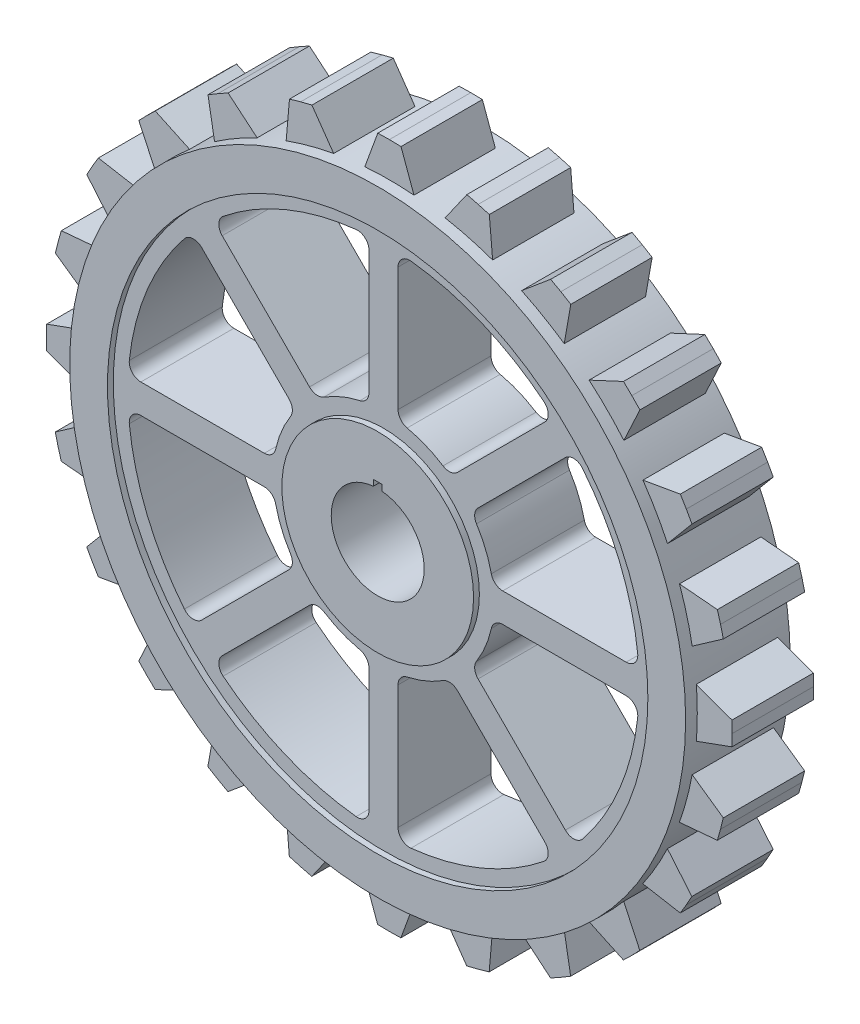
SolidWorks part; units mm, degrees
material "Cast Carbon Steel"
ref_plane "Front Plane" through (0, 0, 0) normal (0, 0, 1) x (1, 0, 0)
ref_plane "Top Plane" through (0, 0, 0) normal (0, 1, 0) x (1, 0, 0)
ref_plane "Right Plane" through (0, 0, 0) normal (1, 0, 0) x (0, 0, -1)
sketch "Sketch1" plane through (0, 0, 0) normal (0, 0, 1) x (1, 0, 0)
  circle A0 centre (-5.965, 13.7526) radius 59000 construction
  circle A1 centre (-5.965, 13.7526) radius 53000
  circle A2 centre (-5.965, 13.7526) radius 46500
extrude "Boss-Extrude4" add sketch "Sketch1" along normal blind 9000 and the other way blind 9000
sketch "Sketch2" plane through (0, 0, 0) normal (0, 0, 1) x (1, 0, 0)
  line L0 (-52494.638, 4371.0565) -> (-52496.6698, -4346.5861)
  line L1 (-58972.0667, 2013.4653) -> (-52494.638, 4371.0565)
  line L2 (-59005.965, 13.7526) -> (-58972.0667, 2013.4653)
  line L3 (-59005.965, 13.7526) -> (-58972.9988, -1985.9757)
  line L4 (-58972.9988, -1985.9757) -> (-52496.6698, -4346.5861)
  line L5 (-49574.6139, 17808.7285) -> (-51832.8684, 9388.6582)
  line L6 (-57477.551, 13345.03) -> (-51832.8684, 9388.6582)
  line L7 (-56991.826, 15285.1515) -> (-57477.551, 13345.03)
  line L8 (-56991.826, 15285.1515) -> (-56441.5191, 17207.9521)
  line L9 (-56441.5191, 17207.9521) -> (-49574.6139, 17808.7285)
  line L10 (-43276.1618, 30032.765) -> (-47636.7427, 22484.0809)
  line L11 (-52065.103, 27766.594) -> (-47636.7427, 22484.0809)
  line L12 (-51093.7884, 29514.8926) -> (-52065.103, 27766.594)
  line L13 (-51093.7884, 29514.8926) -> (-50064.5752, 31229.7454)
  line L14 (-50064.5752, 31229.7454) -> (-43276.1618, 30032.765)
  line L15 (-34028.5108, 40210.1182) -> (-40194.2517, 34047.2507)
  line L16 (-43104.5043, 40295.9105) -> (-40194.2517, 34047.2507)
  line L17 (-41713.7934, 41733.2425) -> (-43104.5043, 40295.9105)
  line L18 (-41713.7934, 41733.2425) -> (-40275.8133, 43123.2832)
  line L19 (-40275.8133, 43123.2832) -> (-34028.5108, 40210.1182)
  line L20 (-22461.873, 47647.2183) -> (-30012.5889, 43290.1566)
  line L21 (-31206.4048, 50079.1273) -> (-30012.5889, 43290.1566)
  line L22 (-29491.0724, 51107.5409) -> (-31206.4048, 50079.1273)
  line L23 (-29491.0724, 51107.5409) -> (-27742.3212, 52078.0405)
  line L24 (-27742.3212, 52078.0405) -> (-22461.873, 47647.2183)
  line L25 (-9364.4957, 51837.2393) -> (-17785.6177, 49582.9099)
  line L26 (-17181.6405, 56449.5343) -> (-17785.6177, 49582.9099)
  line L27 (-15258.5835, 56998.9449) -> (-17181.6405, 56449.5343)
  line L28 (-15258.5835, 56998.9449) -> (-13318.2359, 57483.7654)
  line L29 (-13318.2359, 57483.7654) -> (-9364.4957, 51837.2393)
  line L30 (4371.0565, 52494.638) -> (-4346.5861, 52496.6698)
  line L31 (-1985.9757, 58972.9988) -> (-4346.5861, 52496.6698)
  line L32 (13.7526, 59005.965) -> (-1985.9757, 58972.9988)
  line L33 (13.7526, 59005.965) -> (2013.4653, 58972.0667)
  line L34 (2013.4653, 58972.0667) -> (4371.0565, 52494.638)
  line L35 (17808.7285, 49574.6139) -> (9388.6582, 51832.8684)
  line L36 (13345.03, 57477.551) -> (9388.6582, 51832.8684)
  line L37 (15285.1515, 56991.826) -> (13345.03, 57477.551)
  line L38 (15285.1515, 56991.826) -> (17207.9521, 56441.5191)
  line L39 (17207.9521, 56441.5191) -> (17808.7285, 49574.6139)
  line L40 (30032.765, 43276.1618) -> (22484.0809, 47636.7427)
  line L41 (27766.594, 52065.103) -> (22484.0809, 47636.7427)
  line L42 (29514.8926, 51093.7884) -> (27766.594, 52065.103)
  line L43 (29514.8926, 51093.7884) -> (31229.7454, 50064.5752)
  line L44 (31229.7454, 50064.5752) -> (30032.765, 43276.1618)
  line L45 (40210.1182, 34028.5108) -> (34047.2507, 40194.2517)
  line L46 (40295.9105, 43104.5043) -> (34047.2507, 40194.2517)
  line L47 (41733.2425, 41713.7934) -> (40295.9105, 43104.5043)
  line L48 (41733.2425, 41713.7934) -> (43123.2832, 40275.8133)
  line L49 (43123.2832, 40275.8133) -> (40210.1182, 34028.5108)
  line L50 (47647.2183, 22461.873) -> (43290.1566, 30012.5889)
  line L51 (50079.1273, 31206.4048) -> (43290.1566, 30012.5889)
  line L52 (51107.5409, 29491.0724) -> (50079.1273, 31206.4048)
  line L53 (51107.5409, 29491.0724) -> (52078.0405, 27742.3212)
  line L54 (52078.0405, 27742.3212) -> (47647.2183, 22461.873)
  line L55 (51837.2393, 9364.4957) -> (49582.9099, 17785.6177)
  line L56 (56449.5343, 17181.6405) -> (49582.9099, 17785.6177)
  line L57 (56998.9449, 15258.5835) -> (56449.5343, 17181.6405)
  line L58 (56998.9449, 15258.5835) -> (57483.7654, 13318.2359)
  line L59 (57483.7654, 13318.2359) -> (51837.2393, 9364.4957)
  line L60 (52494.638, -4371.0565) -> (52496.6698, 4346.5861)
  line L61 (58972.9988, 1985.9757) -> (52496.6698, 4346.5861)
  line L62 (59005.965, -13.7526) -> (58972.9988, 1985.9757)
  line L63 (59005.965, -13.7526) -> (58972.0667, -2013.4653)
  line L64 (58972.0667, -2013.4653) -> (52494.638, -4371.0565)
  line L65 (49574.6139, -17808.7285) -> (51832.8684, -9388.6582)
  line L66 (57477.551, -13345.03) -> (51832.8684, -9388.6582)
  line L67 (56991.826, -15285.1515) -> (57477.551, -13345.03)
  line L68 (56991.826, -15285.1515) -> (56441.5191, -17207.9521)
  line L69 (56441.5191, -17207.9521) -> (49574.6139, -17808.7285)
  line L70 (43276.1618, -30032.765) -> (47636.7427, -22484.0809)
  line L71 (52065.103, -27766.594) -> (47636.7427, -22484.0809)
  line L72 (51093.7884, -29514.8926) -> (52065.103, -27766.594)
  line L73 (51093.7884, -29514.8926) -> (50064.5752, -31229.7454)
  line L74 (50064.5752, -31229.7454) -> (43276.1618, -30032.765)
  line L75 (34028.5108, -40210.1182) -> (40194.2517, -34047.2507)
  line L76 (43104.5043, -40295.9105) -> (40194.2517, -34047.2507)
  line L77 (41713.7934, -41733.2425) -> (43104.5043, -40295.9105)
  line L78 (41713.7934, -41733.2425) -> (40275.8133, -43123.2832)
  line L79 (40275.8133, -43123.2832) -> (34028.5108, -40210.1182)
  line L80 (22461.873, -47647.2183) -> (30012.5889, -43290.1566)
  line L81 (31206.4048, -50079.1273) -> (30012.5889, -43290.1566)
  line L82 (29491.0724, -51107.5409) -> (31206.4048, -50079.1273)
  line L83 (29491.0724, -51107.5409) -> (27742.3212, -52078.0405)
  line L84 (27742.3212, -52078.0405) -> (22461.873, -47647.2183)
  line L85 (9364.4957, -51837.2393) -> (17785.6177, -49582.9099)
  line L86 (17181.6405, -56449.5343) -> (17785.6177, -49582.9099)
  line L87 (15258.5835, -56998.9449) -> (17181.6405, -56449.5343)
  line L88 (15258.5835, -56998.9449) -> (13318.2359, -57483.7654)
  line L89 (13318.2359, -57483.7654) -> (9364.4957, -51837.2393)
  line L90 (-4371.0565, -52494.638) -> (4346.5861, -52496.6698)
  line L91 (1985.9757, -58972.9988) -> (4346.5861, -52496.6698)
  line L92 (-13.7526, -59005.965) -> (1985.9757, -58972.9988)
  line L93 (-13.7526, -59005.965) -> (-2013.4653, -58972.0667)
  line L94 (-2013.4653, -58972.0667) -> (-4371.0565, -52494.638)
  line L95 (-17808.7285, -49574.6139) -> (-9388.6582, -51832.8684)
  line L96 (-13345.03, -57477.551) -> (-9388.6582, -51832.8684)
  line L97 (-15285.1515, -56991.826) -> (-13345.03, -57477.551)
  line L98 (-15285.1515, -56991.826) -> (-17207.9521, -56441.5191)
  line L99 (-17207.9521, -56441.5191) -> (-17808.7285, -49574.6139)
  line L100 (-30032.765, -43276.1618) -> (-22484.0809, -47636.7427)
  line L101 (-27766.594, -52065.103) -> (-22484.0809, -47636.7427)
  line L102 (-29514.8926, -51093.7884) -> (-27766.594, -52065.103)
  line L103 (-29514.8926, -51093.7884) -> (-31229.7454, -50064.5752)
  line L104 (-31229.7454, -50064.5752) -> (-30032.765, -43276.1618)
  line L105 (-40210.1182, -34028.5108) -> (-34047.2507, -40194.2517)
  line L106 (-40295.9105, -43104.5043) -> (-34047.2507, -40194.2517)
  line L107 (-41733.2425, -41713.7934) -> (-40295.9105, -43104.5043)
  line L108 (-41733.2425, -41713.7934) -> (-43123.2832, -40275.8133)
  line L109 (-43123.2832, -40275.8133) -> (-40210.1182, -34028.5108)
  line L110 (-47647.2183, -22461.873) -> (-43290.1566, -30012.5889)
  line L111 (-50079.1273, -31206.4048) -> (-43290.1566, -30012.5889)
  line L112 (-51107.5409, -29491.0724) -> (-50079.1273, -31206.4048)
  line L113 (-51107.5409, -29491.0724) -> (-52078.0405, -27742.3212)
  line L114 (-52078.0405, -27742.3212) -> (-47647.2183, -22461.873)
  line L115 (-51837.2393, -9364.4957) -> (-49582.9099, -17785.6177)
  line L116 (-56449.5343, -17181.6405) -> (-49582.9099, -17785.6177)
  line L117 (-56998.9449, -15258.5835) -> (-56449.5343, -17181.6405)
  line L118 (-56998.9449, -15258.5835) -> (-57483.7654, -13318.2359)
  line L119 (-57483.7654, -13318.2359) -> (-51837.2393, -9364.4957)
  circle A0 centre (-5.965, 13.7526) radius 59000 construction
  point P125 (0, 0)
  dimension "D1" = 24
extrude "Boss-Extrude5" add sketch "Sketch2" along normal blind 7000 and the other way blind 7000
sketch "Sketch3" plane through (0, 0, 0) normal (0, 0, 1) x (1, 0, 0)
  line L2 (2500, 20512.1915) -> (2500, 41758.2327)
  line L3 (12736.5428, 16272.0767) -> (27759.7626, 31295.2965)
  line L4 (16272.0767, 12736.5428) -> (31295.2965, 27759.7626)
  line L5 (20512.1915, 2500) -> (41758.2327, 2500)
  line L6 (20512.1915, -2500) -> (41758.2327, -2500)
  line L7 (16272.0767, -12736.5428) -> (31295.2965, -27759.7626)
  line L8 (12736.5428, -16272.0767) -> (27759.7626, -31295.2965)
  line L9 (2500, -20512.1915) -> (2500, -41758.2327)
  line L10 (-2500, -20512.1915) -> (-2500, -41758.2327)
  line L11 (-12736.5428, -16272.0767) -> (-27759.7626, -31295.2965)
  line L12 (-16272.0767, -12736.5428) -> (-31295.2965, -27759.7626)
  line L13 (-20512.1915, -2500) -> (-41758.2327, -2500)
  line L14 (-20512.1915, 2500) -> (-41758.2327, 2500)
  line L15 (-16272.0767, 12736.5428) -> (-31295.2965, 27759.7626)
  line L16 (-12736.5428, 16272.0767) -> (-27759.7626, 31295.2965)
  line L17 (-2500, 20512.1915) -> (-2500, 41758.2327)
  arc A2 (27600.099, 34267.1058) -> (4714.2857, 43746.72) centre (0, 0) ccw
  arc A3 (10244.0121, 16001.8816) -> (4071.4286, 18558.6494) centre (0, 0) ccw
  arc A4 (31295.2965, 27759.7626) -> (34267.1058, 27600.099) centre (32709.51, 26345.549) cw
  arc A5 (2500, 20512.1915) -> (4071.4286, 18558.6494) centre (4500, 20512.1915) ccw
  arc A6 (12736.5428, 16272.0767) -> (10244.0121, 16001.8816) centre (11322.3292, 17686.2902) cw
  arc A7 (16272.0767, 12736.5428) -> (16001.8816, 10244.0121) centre (17686.2902, 11322.3292) ccw
  arc A8 (27600.099, 34267.1058) -> (27759.7626, 31295.2965) centre (26345.549, 32709.51) cw
  arc A9 (2500, 41758.2327) -> (4714.2857, 43746.72) centre (4500, 41758.2327) cw
  arc A10 (43746.72, 4714.2857) -> (34267.1058, 27600.099) centre (0, 0) ccw
  arc A11 (43746.72, 4714.2857) -> (41758.2327, 2500) centre (41758.2327, 4500) cw
  arc A12 (20512.1915, 2500) -> (18558.6494, 4071.4286) centre (20512.1915, 4500) cw
  arc A13 (18558.6494, 4071.4286) -> (16001.8816, 10244.0121) centre (0, 0) ccw
  arc A14 (41758.2327, -2500) -> (43746.72, -4714.2857) centre (41758.2327, -4500) cw
  arc A15 (20512.1915, -2500) -> (18558.6494, -4071.4286) centre (20512.1915, -4500) ccw
  arc A16 (34267.1058, -27600.099) -> (43746.72, -4714.2857) centre (0, 0) ccw
  arc A17 (34267.1058, -27600.099) -> (31295.2965, -27759.7626) centre (32709.51, -26345.549) cw
  arc A18 (16272.0767, -12736.5428) -> (16001.8816, -10244.0121) centre (17686.2902, -11322.3292) cw
  arc A19 (16001.8816, -10244.0121) -> (18558.6494, -4071.4286) centre (0, 0) ccw
  arc A20 (27759.7626, -31295.2965) -> (27600.099, -34267.1058) centre (26345.549, -32709.51) cw
  arc A21 (12736.5428, -16272.0767) -> (10244.0121, -16001.8816) centre (11322.3292, -17686.2902) ccw
  arc A22 (4714.2857, -43746.72) -> (27600.099, -34267.1058) centre (0, 0) ccw
  arc A23 (4714.2857, -43746.72) -> (2500, -41758.2327) centre (4500, -41758.2327) cw
  arc A24 (2500, -20512.1915) -> (4071.4286, -18558.6494) centre (4500, -20512.1915) cw
  arc A25 (4071.4286, -18558.6494) -> (10244.0121, -16001.8816) centre (0, 0) ccw
  arc A26 (-2500, -41758.2327) -> (-4714.2857, -43746.72) centre (-4500, -41758.2327) cw
  arc A27 (-2500, -20512.1915) -> (-4071.4286, -18558.6494) centre (-4500, -20512.1915) ccw
  arc A28 (-27600.099, -34267.1058) -> (-4714.2857, -43746.72) centre (0, 0) ccw
  arc A29 (-27600.099, -34267.1058) -> (-27759.7626, -31295.2965) centre (-26345.549, -32709.51) cw
  arc A30 (-12736.5428, -16272.0767) -> (-10244.0121, -16001.8816) centre (-11322.3292, -17686.2902) cw
  arc A31 (-10244.0121, -16001.8816) -> (-4071.4286, -18558.6494) centre (0, 0) ccw
  arc A32 (-31295.2965, -27759.7626) -> (-34267.1058, -27600.099) centre (-32709.51, -26345.549) cw
  arc A33 (-16272.0767, -12736.5428) -> (-16001.8816, -10244.0121) centre (-17686.2902, -11322.3292) ccw
  arc A34 (-43746.72, -4714.2857) -> (-34267.1058, -27600.099) centre (0, 0) ccw
  arc A35 (-43746.72, -4714.2857) -> (-41758.2327, -2500) centre (-41758.2327, -4500) cw
  arc A36 (-20512.1915, -2500) -> (-18558.6494, -4071.4286) centre (-20512.1915, -4500) cw
  arc A37 (-18558.6494, -4071.4286) -> (-16001.8816, -10244.0121) centre (0, 0) ccw
  arc A38 (-41758.2327, 2500) -> (-43746.72, 4714.2857) centre (-41758.2327, 4500) cw
  arc A39 (-20512.1915, 2500) -> (-18558.6494, 4071.4286) centre (-20512.1915, 4500) ccw
  arc A40 (-34267.1058, 27600.099) -> (-43746.72, 4714.2857) centre (0, 0) ccw
  arc A41 (-34267.1058, 27600.099) -> (-31295.2965, 27759.7626) centre (-32709.51, 26345.549) cw
  arc A42 (-16272.0767, 12736.5428) -> (-16001.8816, 10244.0121) centre (-17686.2902, 11322.3292) cw
  arc A43 (-16001.8816, 10244.0121) -> (-18558.6494, 4071.4286) centre (0, 0) ccw
  arc A44 (-27759.7626, 31295.2965) -> (-27600.099, 34267.1058) centre (-26345.549, 32709.51) cw
  arc A45 (-12736.5428, 16272.0767) -> (-10244.0121, 16001.8816) centre (-11322.3292, 17686.2902) ccw
  arc A46 (-4714.2857, 43746.72) -> (-27600.099, 34267.1058) centre (0, 0) ccw
  arc A47 (-4714.2857, 43746.72) -> (-2500, 41758.2327) centre (-4500, 41758.2327) cw
  arc A48 (-2500, 20512.1915) -> (-4071.4286, 18558.6494) centre (-4500, 20512.1915) cw
  arc A49 (-4071.4286, 18558.6494) -> (-10244.0121, 16001.8816) centre (0, 0) ccw
  circle A50 centre (0, 0) radius 16500
  circle A51 centre (0, 0) radius 46500
  point P101 (0, 0)
  dimension "D1" = 8
  dimension "D3" = 2000
extrude "Boss-Extrude6" add sketch "Sketch3" along normal blind 8000 and the other way blind 8000
sketch "Sketch4" plane through (0, 0, 0) normal (0, 0, 1) x (1, 0, 0)
  line L1 (-750, 9000) -> (750, 9000)
  line L2 (-750, 9000) -> (-750, 7964.7662)
  line L4 (750, 9000) -> (750, 7964.7662)
  circle A0 centre (0, 0) radius 16500
  arc A1 (-750, 7964.7662) -> (750, 7964.7662) centre (0, 0) ccw
  point P4 (0, 8000)
extrude "Boss-Extrude8" add sketch "Sketch4" along normal blind 9000 and the other way blind 9000
